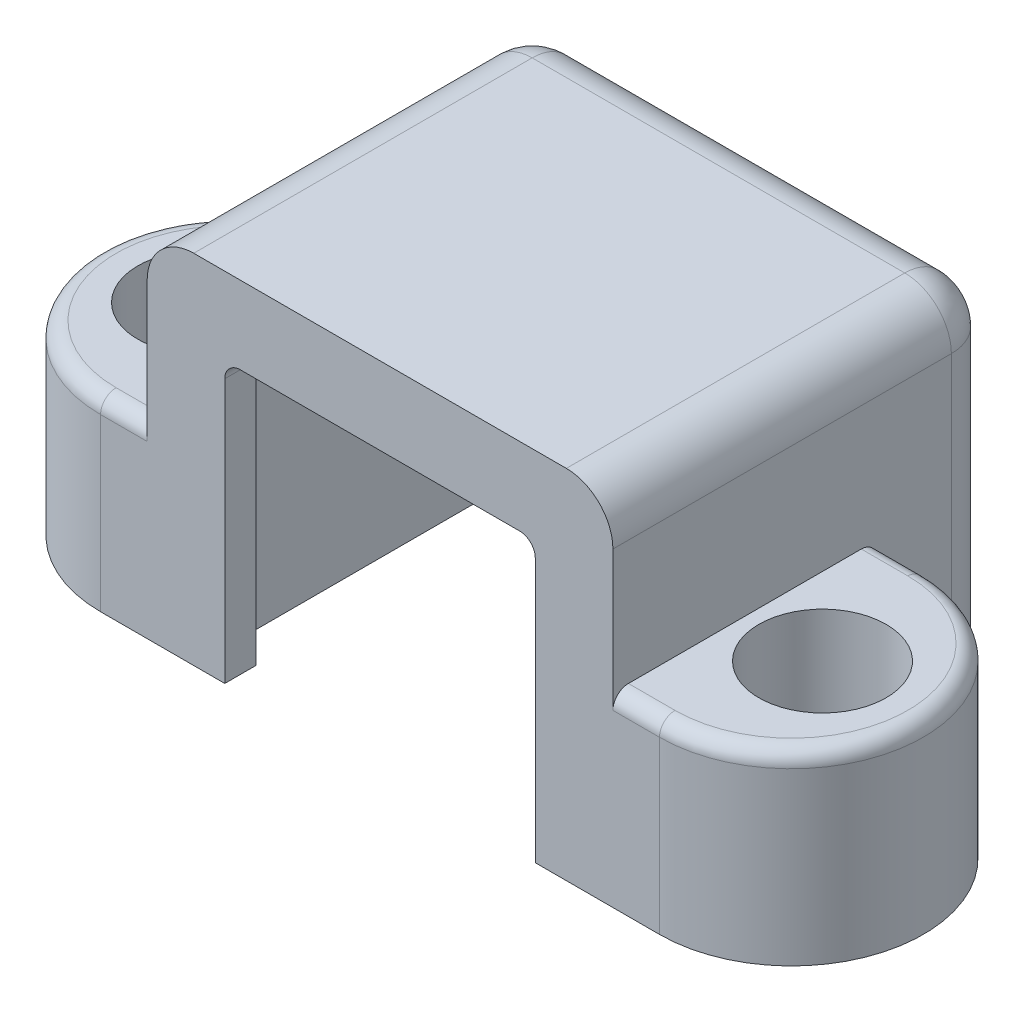
SolidWorks part; units mm, degrees
material "Custom Plastic"
ref_plane "Front Plane" through (0, 0, 0) normal (0, 0, 1) x (1, 0, 0)
ref_plane "Top Plane" through (0, 0, 0) normal (0, 1, 0) x (1, 0, 0)
ref_plane "Right Plane" through (0, 0, 0) normal (1, 0, 0) x (0, 0, -1)
sketch "Sketch1" plane through (0, 0, 0) normal (0, 0, 1) x (1, 0, 0)
  line L0 (0, -210.3757) -> (0, 10308.4069) construction
  line L1 (0, 0) -> (6, 0)
  line L2 (6, 0) -> (6, -10)
  line L3 (0, 1.5) -> (7.5, 1.5)
  line L4 (7.5, 1.5) -> (7.5, -10)
  line L5 (7.5, -10) -> (6, -10)
  line L6 (-7.5, -10) -> (-6, -10)
  line L7 (-7.5, 1.5) -> (-7.5, -10)
  line L8 (0, 1.5) -> (-7.5, 1.5)
  line L9 (-6, 0) -> (-6, -10)
  line L10 (0, 0) -> (-6, 0)
  dimension "D1" = 12
  dimension "D2" = 10
  dimension "D3" = 1.5
extrude "Boss-Extrude1" add sketch "Sketch1" along normal blind 12.4
sketch "Sketch3" plane through (0, -10, 0) normal (0, -1, 0) x (1, 0, 0)
  line L0 (0, -1000) -> (0, 49000) construction
  line L1 (7.5, 0) -> (-7.5, 0) construction
  line L2 (7.5, 3.9) -> (7.5, 12.4)
  line L3 (7.5, 12.4) -> (7.5, 0) construction
  line L4 (7.5, 3.9) -> (9, 3.9)
  line L5 (7.5, 12.4) -> (9, 12.4)
  line L6 (-7.5, 12.4) -> (-9, 12.4)
  line L7 (-7.5, 3.9) -> (-9, 3.9)
  line L8 (-7.5, 3.9) -> (-7.5, 12.4)
  arc A0 (9, 3.9) -> (9, 12.4) centre (9, 8.15) ccw
  arc A1 (-9, 3.9) -> (-9, 12.4) centre (-9, 8.15) cw
  point P5 (0, 0)
  point P7 (0, 0)
  point P8 (0, 0)
  point P10 (7.5, 8.15)
  point P22 (-7.5, 8.15)
  dimension "D1" = 8.5
  dimension "D2" = 1.5
extrude "Boss-Extrude2" add sketch "Sketch3" against normal blind 6
sketch "Sketch4" plane through (0, -10, 0) normal (0, -1, 0) x (1, 0, 0)
  line L1 (0, -1000) -> (0, 49000) construction
  circle A0 centre (-10, 8.15) radius 2.05
  circle A2 centre (10, 8.15) radius 2.05
  arc A3 (-9, 12.4) -> (-9, 3.9) centre (-9, 8.15) ccw construction
  point P3 (-9, 8.15)
  dimension "D1" = 4.1
  dimension "D2" = 1
extrude "Cut-Extrude1" cut sketch "Sketch4" against normal up to surface (6 mm away) up to face at (9.3125, -4, 8.15)
fillet "Fillet1" radius 1.5 2 edges at (-7.5, 1.5, 6.2) (7.5, 1.5, 6.2)
fillet "Fillet2" radius 0.5 6 edges at (8.25, -4, 3.9) (8.25, -4, 12.4) (13.25, -4, 8.15) (-8.25, -4, 12.4) (-13.25, -4, 8.15) (-8.25, -4, 3.9)
fillet "Fillet3" radius 1 2 edges at (-6, 0, 6.2) (6, 0, 6.2)
sketch "Sketch6" plane through (0, 0, 12.4) normal (0, 0, -1) x (-1, 0, 0)
  line L0 (6, -10) -> (6, -1) construction
  line L1 (5, 0) -> (-5, 0) construction
  line L2 (-6, -1) -> (-6, -10) construction
  line L3 (6, -10) -> (6, -1)
  line L4 (5, 0) -> (-5, 0)
  line L5 (-6, -1) -> (-6, -10)
  line L6 (5, -10) -> (5, -1)
  line L7 (5, -1) -> (-5, -1)
  line L8 (-5, -1) -> (-5, -10)
  line L9 (-5, -10) -> (-6, -10)
  line L10 (5, -10) -> (6, -10)
  arc A0 (6, -1) -> (5, 0) centre (5, -1) ccw construction
  arc A1 (-5, 0) -> (-6, -1) centre (-5, -1) ccw construction
  arc A2 (6, -1) -> (5, 0) centre (5, -1) ccw
  arc A3 (-5, 0) -> (-6, -1) centre (-5, -1) ccw
  arc A4 (5, -1) -> (5, -1) centre (5, -1) ccw
  arc A5 (-5, -1) -> (-5, -1) centre (-5, -1) ccw
  dimension "D1" = 1
extrude "Boss-Extrude3" add sketch "Sketch6" along normal blind 1
fillet "Fillet4" radius 0.5 2 edges at (-5, -1, 11.9) (5, -1, 11.9)
ref_plane "Plane1" through (0, 0, 5.55) normal (0, 0, -1) x (-1, 0, 0)
sketch "Sketch7" plane through (0, 0, 5.55) normal (0, 0, -1) x (-1, 0, 0)
  line L0 (-6, -2) -> (-4, 0)
  line L1 (-6, -1) -> (-6, -10) construction
  line L2 (5, 0) -> (-5, 0) construction
  line L3 (5, 0) -> (-5, 0) construction
  line L4 (-6, -1) -> (-6, -10) construction
  line L5 (-4, 0) -> (-5, 0)
  line L6 (-6, -1) -> (-6, -2)
  line L7 (0, -1000) -> (0, 49000) construction
  line L8 (6, -1) -> (6, -2)
  line L9 (4, 0) -> (5, 0)
  line L10 (6, -2) -> (4, 0)
  arc A0 (-5, 0) -> (-6, -1) centre (-5, -1) ccw construction
  arc A1 (-5, 0) -> (-6, -1) centre (-5, -1) ccw
  arc A2 (5, 0) -> (6, -1) centre (5, -1) cw
  dimension "D1" = 45
  dimension "D2" = 2
extrude "Boss-Extrude4" add sketch "Sketch7" along normal blind 1 contours L5 A1 L6 L0 | A2 L9 L10 L8 region at (5.28, -0.72, 5.55) region at (-5.28, -0.72, 5.55)
fillet "Fillet5" radius 1.5 5 edges at (-7.5, -5, 0) (-7.0607, 1.0607, 0) (0, 1.5, 0) (7.0607, 1.0607, 0) (7.5, -5, 0)
equation "\"Hole_Diameter\"= 4.1mm"
equation "\"Hole_Depth\"= 6mm"
equation "\"D1@Sketch4\"=\"Hole_Diameter\""
equation "\"D1@Boss-Extrude2\"=\"Hole_Depth\""
